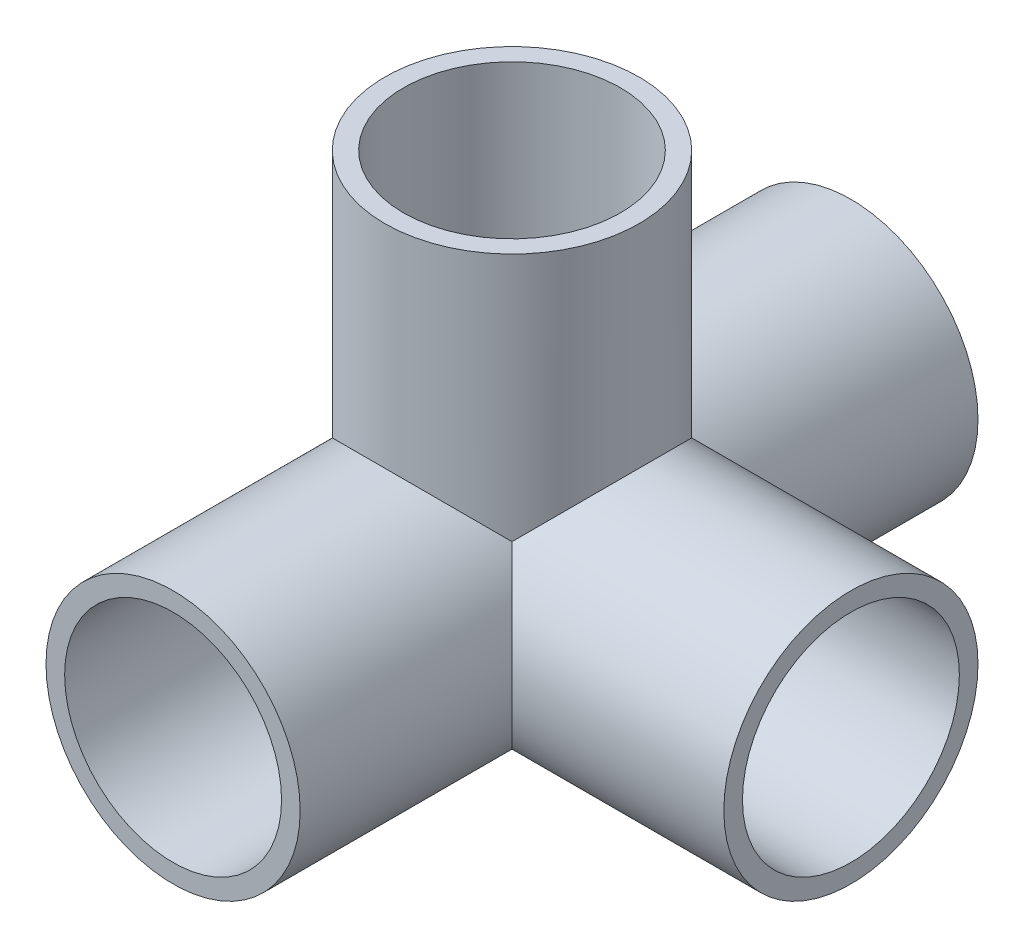
SolidWorks part; units mm, degrees
ref_plane "정면" through (0, 0, 0) normal (0, 0, 1) x (1, 0, 0)
ref_plane "윗면" through (0, 0, 0) normal (0, 1, 0) x (1, 0, 0)
ref_plane "우측면" through (0, 0, 0) normal (1, 0, 0) x (0, 0, -1)
sketch "스케치5" plane through (0, 0, 0) normal (0, 0, 1) x (1, 0, 0)
  circle A0 centre (0, 0) radius 15
  dimension "D1" = 30
extrude "보스-돌출1" add sketch "스케치5" along normal blind 40 and the other way blind 40
sketch "스케치6" plane through (0, 0, 0) normal (0, 1, 0) x (1, 0, 0)
  circle A0 centre (0, 0) radius 15
  dimension "D1" = 30
extrude "보스-돌출2" add sketch "스케치6" along normal blind 40
sketch "스케치7" plane through (0, 0, 0) normal (1, 0, 0) x (0, 0, -1)
  circle A0 centre (0, 0) radius 15
  dimension "D1" = 30
extrude "보스-돌출3" add sketch "스케치7" along normal blind 40
shell "쉘1" thickness 2.2 removed face at (15, 0, 40) removed face at (0, 40, 15) removed face at (40, 0, -15) removed face at (15, 0, -40)
